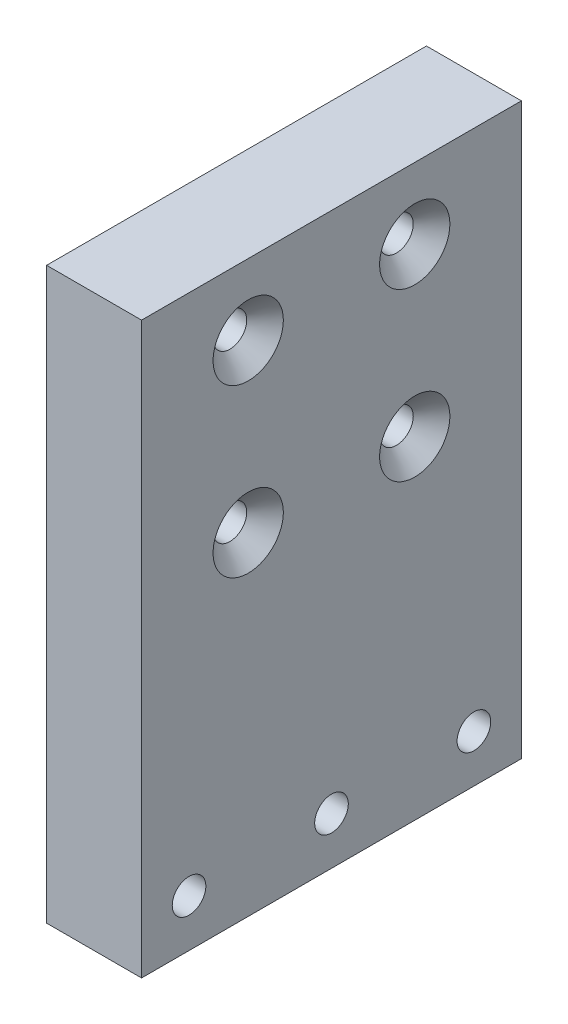
SolidWorks part; units mm, degrees
material "Nylon 6/10"
ref_plane "Front Plane" through (0, 0, 0) normal (0, 0, 1) x (1, 0, 0)
ref_plane "Top Plane" through (0, 0, 0) normal (0, 1, 0) x (1, 0, 0)
ref_plane "Right Plane" through (0, 0, 0) normal (1, 0, 0) x (0, 0, -1)
sketch "Sketch1" plane through (0, 0, 0) normal (1, 0, 0) x (0, 0, -1)
  line L1 (-25.4, -38.1) -> (25.4, -38.1)
  line L2 (-25.4, -38.1) -> (-25.4, 38.1)
  line L3 (-25.4, 38.1) -> (25.4, 38.1)
  line L4 (25.4, -38.1) -> (25.4, 38.1)
  line L5 (-25.4, -38.1) -> (25.4, 38.1) construction
  line L6 (-25.4, 38.1) -> (25.4, -38.1) construction
  point P0 (0, 0)
  dimension "D1" = 50.8
  dimension "D2" = 76.2
extrude "Boss-Extrude1" add sketch "Sketch1" along normal blind 12.7
hole_wizard "CSK for M4 Flat Head Machine Screw1" positions "Sketch3" profile "Sketch2" countersink size "M4" standard "ANSI Metric" end condition through all
sketch "Sketch3" plane through (12.7, 0, 0) normal (1, 0, 0) x (0, 0, -1)
  line L1 (-11.1369, 6.35) -> (11.1369, 6.35) construction
  line L2 (-11.1369, 6.35) -> (-11.1369, 28.6239) construction
  line L3 (-11.1369, 28.6239) -> (11.1369, 28.6239) construction
  line L4 (11.1369, 6.35) -> (11.1369, 28.6239) construction
  line L5 (-11.1369, 6.35) -> (11.1369, 28.6239) construction
  line L6 (-11.1369, 28.6239) -> (11.1369, 6.35) construction
  line L8 (25.4, 38.1) -> (-25.4, 38.1) construction
  point P219 (11.1369, 28.6239)
  point P223 (-11.1369, 28.6239)
  point P225 (-11.1369, 6.35)
  point P227 (11.1369, 6.35)
  dimension "D1" = 31.5
  dimension "D2" = 31.75
sketch "Sketch2" plane through (12.7, 28.6239, -11.1369) normal (0, 1, 0) x (0, 0, -1)
  line L0 (0, 0) -> (0, 12.7)
  line L1 (0, 12.7) -> (2.25, 12.7)
  line L2 (2.25, 12.7) -> (2.25, 2.45)
  line L3 (2.25, 2.45) -> (4.7, 0)
  line L5 (4.7, 0) -> (0, 0)
  line L6 (-2.25, 2.45) -> (-4.7, 0) construction
  line L11 (0, -6.35) -> (0, 107.95) construction
  dimension "Thru Hole Dia." = 4.5
  dimension "Thru Hole Depth" = 12.7
  dimension "Near C'Sink Dia." = 9.4
  dimension "Near C'Sink Angle" = 90
hole_wizard "CBORE for #8 Binding Head Machine Screw1" positions "Sketch5" profile "Sketch4" counterbore size "#8" standard "ANSI Inch" end condition through all
sketch "Sketch5" plane through (0, 0, 0) normal (-1, 0, 0) x (0, 0, 1)
  line L0 (-25.4, -31.75) -> (25.4, -31.75) construction
  line L1 (-25.4, -38.1) -> (-25.4, 38.1) construction
  line L2 (25.4, 38.1) -> (25.4, -38.1) construction
  line L4 (25.4, -38.1) -> (-25.4, -38.1) construction
  line L5 (0, -38.1) -> (0, 0) construction
  point P0 (-19.05, -31.75)
  point P2 (0, -31.75)
  point P4 (19.05, -31.75)
  dimension "D1" = 6.35
  dimension "D2" = 6.35
  dimension "D3" = 6.35
sketch "Sketch4" plane through (0, -31.75, -19.05) normal (0, 1, 0) x (0, 0, 1)
  line L0 (0, 0) -> (0, 12.7)
  line L1 (0, 12.7) -> (2.2479, 12.7)
  line L3 (2.2479, 12.7) -> (2.2479, 2.667)
  line L4 (2.2479, 2.667) -> (4.7625, 2.667)
  line L5 (4.7625, 2.667) -> (4.7625, 0)
  line L7 (4.7625, 0) -> (0, 0)
  line L11 (0, -6.35) -> (0, 107.95) construction
  dimension "Thru Hole Dia." = 4.4958
  dimension "Thru Hole Depth" = 12.7
  dimension "C'Bore Dia." = 9.525
  dimension "C'Bore Depth" = 2.667
